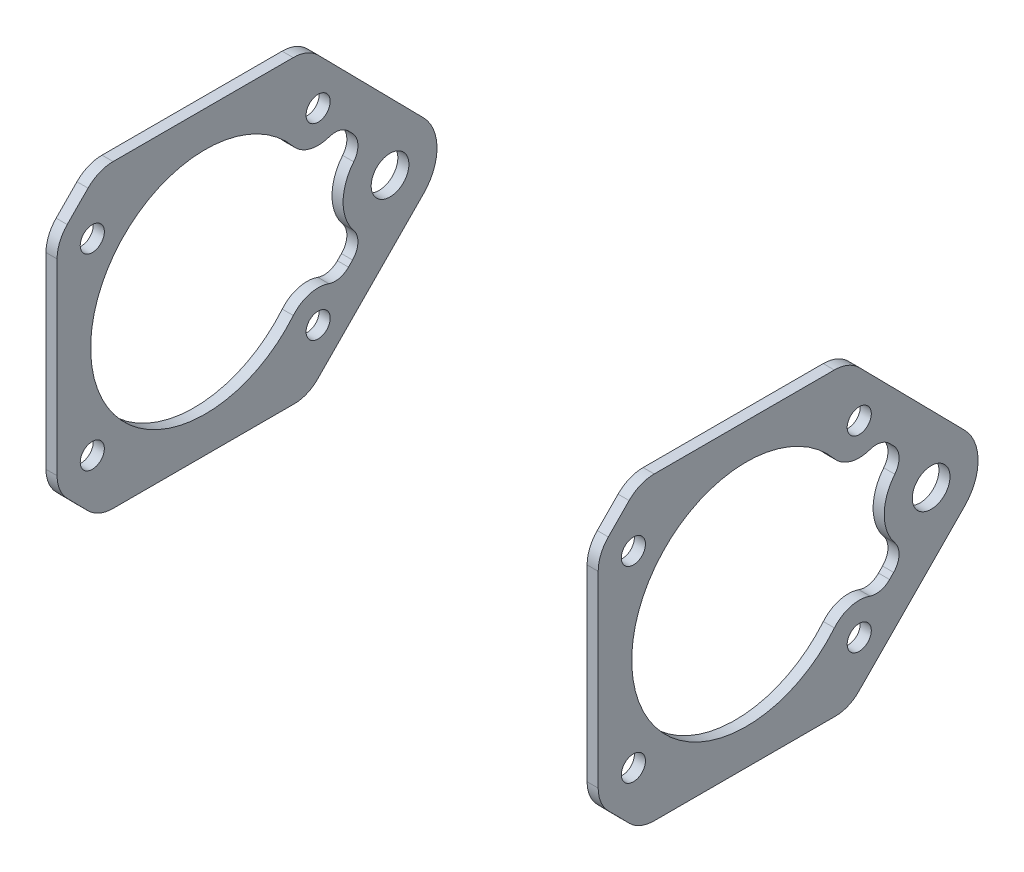
SolidWorks part; units mm, degrees
ref_plane "Front Plane" through (0, 0, 0) normal (0, 0, 1) x (1, 0, 0)
ref_plane "Top Plane" through (0, 0, 0) normal (0, 1, 0) x (1, 0, 0)
ref_plane "Right Plane" through (0, 0, 0) normal (1, 0, 0) x (0, 0, -1)
sketch "Sketch1" plane through (37.35, 0, 0) normal (-1, 0, 0) x (0, 0, 1)
  line L0 (-4.5233, 4.4567) -> (9.7073, 18.9)
  line L1 (13.0998, 20.32) -> (37.4636, 20.32)
  line L2 (45.0415, 12.7) -> (45.0415, -12.7)
  line L4 (37.4636, -20.32) -> (12.9337, -20.32)
  line L5 (9.8239, -19.0184) -> (-4.5233, -4.4567)
  line L7 (5.6234, -7.9694) -> (5.0726, -7.4104)
  line L8 (5.0726, 7.4104) -> (5.6234, 7.9694)
  line L9 (43.6715, 16.0425) -> (40.8561, 18.9)
  line L10 (11.43, 20.32) -> (147.2651, 20.32) construction
  line L11 (25.2817, 20.32) -> (25.2817, 7.2204) construction
  line L12 (0, 0) -> (51.1358, 0) construction
  line L13 (43.6715, -16.0425) -> (40.8561, -18.9)
  line L14 (157.5652, -20.32) -> (0, -20.32) construction
  arc A0 (37.4636, 20.32) -> (40.8561, 18.9) centre (37.4636, 15.5575) cw
  arc A1 (13.0842, -9.9091) -> (13.0842, 9.9091) centre (25.0031, 0) ccw
  arc A2 (4.9157, 4.0198) -> (4.9157, -4.0198) centre (0, 0) cw
  arc A3 (-4.5233, 4.4567) -> (-4.5233, -4.4567) centre (0, 0) ccw
  arc A5 (8.2767, -8.5824) -> (13.0842, -9.9091) centre (9.7272, -12.7) cw
  arc A6 (13.0842, 9.9091) -> (8.2767, 8.5824) centre (9.7272, 12.7) cw
  arc A7 (8.2767, -8.5824) -> (5.6234, -7.9694) centre (7.4327, -6.1867) cw
  arc A8 (5.0726, -7.4104) -> (4.9157, -4.0198) centre (6.882, -5.6277) cw
  arc A9 (9.8239, -19.0184) -> (12.9337, -20.32) centre (12.9337, -15.9544) ccw
  arc A10 (43.6715, -16.0425) -> (45.0415, -12.7) centre (40.279, -12.7) ccw
  arc A11 (45.0415, 12.7) -> (43.6715, 16.0425) centre (40.279, 12.7) ccw
  arc A12 (13.0998, 20.32) -> (9.7073, 18.9) centre (13.0998, 15.5575) ccw
  arc A13 (37.5725, -16.6187) -> (42.6573, -8.5739) centre (40.279, -12.7) ccw construction
  arc A14 (42.6573, 8.5739) -> (37.5725, 16.6187) centre (40.279, 12.7) ccw construction
  arc A17 (4.9157, 4.0198) -> (5.0726, 7.4104) centre (6.882, 5.6277) cw
  arc A18 (5.6234, 7.9694) -> (8.2767, 8.5824) centre (7.4327, 6.1867) cw
  circle A19 centre (9.7272, 12.7) radius 1.632 construction
  circle A20 centre (9.7272, 12.7) radius 1.632
  circle A21 centre (40.279, 12.7) radius 1.632 construction
  circle A22 centre (40.279, -12.7) radius 1.632 construction
  circle A23 centre (9.7272, -12.7) radius 1.632 construction
  circle A24 centre (40.279, 12.7) radius 1.6319
  circle A25 centre (40.279, -12.7) radius 1.6319
  circle A26 centre (9.7272, -12.7) radius 1.632
  circle A27 centre (25.0031, 0) radius 15.5 construction
  arc A28 (37.4636, -20.32) -> (40.8561, -18.9) centre (37.4636, -15.5575) ccw
  dimension "D1" = 6.35
  dimension "D2" = 2.54
  dimension "D3" = 4.7625
  dimension "D4" = 4.7625
extrude "Boss-Extrude1" add sketch "Sketch1" along normal blind 1.5
sketch "Sketch4" [suppressed] plane through (35.85, 0, 0) normal (-1, 0, 0) x (0, 0, 1)
  line L0 (18.3837, 17.4625) -> (31.6225, 17.4625)
  line L1 (37.4636, 20.32) -> (13.0998, 20.32) construction
  line L2 (18.3837, -17.4625) -> (31.6225, -17.4625)
  line L3 (12.9337, -20.32) -> (37.4636, -20.32) construction
  arc A0 (18.3837, -17.4625) -> (31.6225, -17.4625) centre (25.0031, 0) ccw
  arc A1 (31.6225, 17.4625) -> (18.3837, 17.4625) centre (25.0031, 0) ccw
  arc A2 (13.0842, -9.9091) -> (13.0842, 9.9091) centre (25.0031, 0) ccw construction
  dimension "D1" = 3.175
extrude "Boss-Extrude2" [suppressed] add sketch "Sketch4" against normal up to surface (1.5 mm away) up to face at (37.35, -0.0064, 26.3877)
fillet "Fillet1" [suppressed] radius 6.35
hole_wizard "#10 Clearance Hole1" positions "Sketch2" profile "Sketch3" hole size "#10" standard "ANSI Inch" end condition up to next
sketch "Sketch2" plane through (35.85, 0, 0) normal (-1, 0, 0) x (0, 0, 1)
  point P0 (0, 0)
sketch "Sketch3" plane through (35.85, 0, 0) normal (0, 1, 0) x (0, 0, 1)
  line L0 (0, 0) -> (0, 1.5)
  line L1 (0, 1.5) -> (2.5527, 1.5)
  line L2 (2.5527, 1.5) -> (2.5527, 0)
  line L5 (2.5527, 0) -> (0, 0)
  line L11 (0, -6.35) -> (0, 107.95) construction
  dimension "Thru Hole Dia." = 5.1054
  dimension "Thru Hole Depth" = 1.5
mirror "Mirror2" about plane through (0, 0, 0) normal (1, 0, 0) of bodies 102
equation "\"D1@Boss-Extrude1\"=1.5mm"
equation "\"D3@Sketch1\"=\"D4@Sketch1\""
